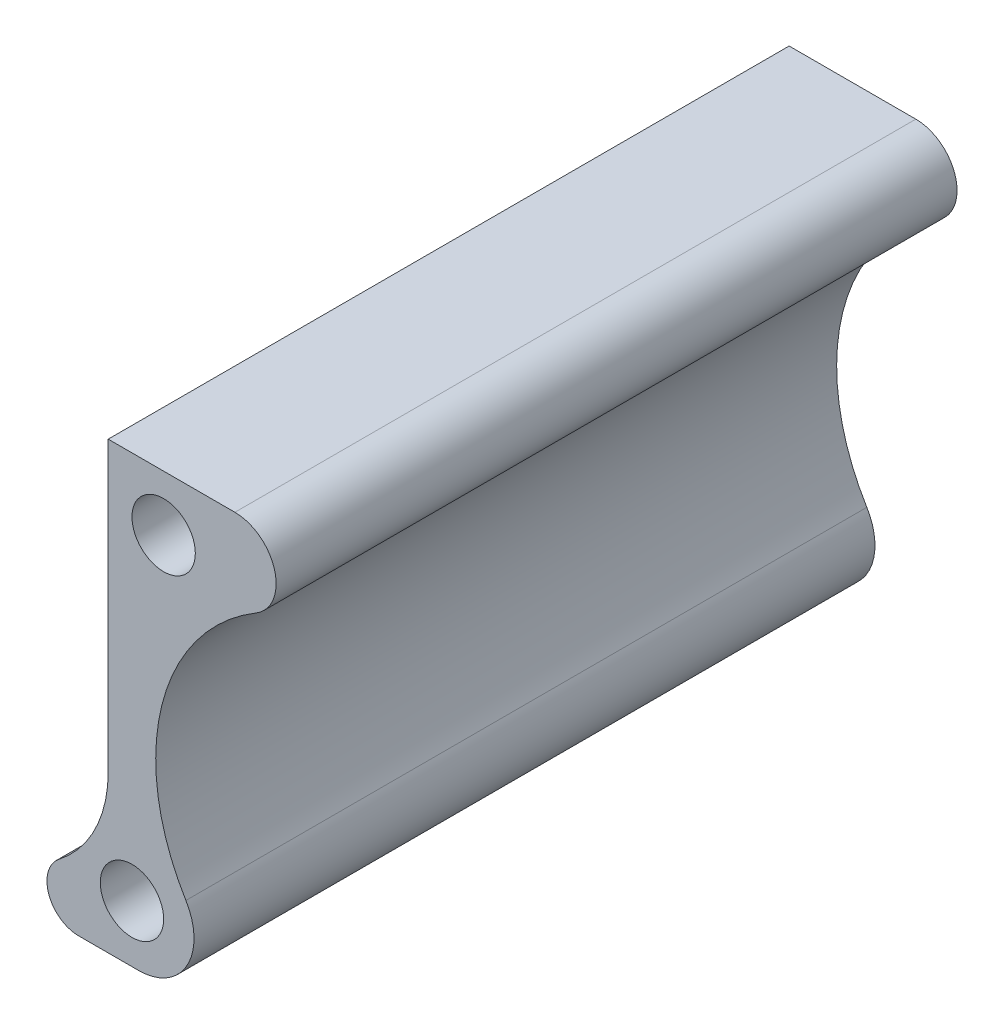
SolidWorks part; units mm, degrees
ref_plane "Front Plane" through (0, 0, 0) normal (0, 0, 1) x (1, 0, 0)
ref_plane "Top Plane" through (0, 0, 0) normal (0, 1, 0) x (1, 0, 0)
ref_plane "Right Plane" through (0, 0, 0) normal (1, 0, 0) x (0, 0, -1)
sketch "Sketch1" plane through (0, 0, 0) normal (0, 0, 1) x (1, 0, 0)
  line L0 (-16, 38) -> (16, 38)
  line L1 (-20.1, 6.5) -> (20.1, 6.5) construction
  line L2 (-20.1, 6.5) -> (-20.1, 2.3) construction
  line L3 (-20.1, 2.3) -> (20.1, 2.3) construction
  line L4 (20.1, 6.5) -> (20.1, 2.3) construction
  line L5 (-20.1, 6.5) -> (20.1, 2.3) construction
  line L6 (-20.1, 2.3) -> (20.1, 6.5) construction
  line L7 (-26.1, 7) -> (26.1, 7) construction
  line L8 (-26.1, 7) -> (-26.1, 1.8) construction
  line L9 (-26.1, 1.8) -> (26.1, 1.8) construction
  line L10 (26.1, 7) -> (26.1, 1.8) construction
  line L11 (-26.1, 7) -> (26.1, 1.8) construction
  line L12 (-26.1, 1.8) -> (26.1, 7) construction
  line L13 (29.1, 9.9) -> (-29.1, 9.9) construction
  line L14 (29.1, 9.9) -> (29.1, -1.1) construction
  line L15 (29.1, -1.1) -> (-29.1, -1.1) construction
  line L16 (-29.1, 9.9) -> (-29.1, -1.1) construction
  line L17 (29.1, 9.9) -> (-29.1, -1.1) construction
  line L18 (29.1, -1.1) -> (-29.1, 9.9) construction
  line L19 (32.1, 11.8) -> (-32.1, 11.8) construction
  line L20 (32.1, 11.8) -> (32.1, -3) construction
  line L21 (32.1, -3) -> (-32.1, -3) construction
  line L22 (-32.1, 11.8) -> (-32.1, -3) construction
  line L23 (32.1, 11.8) -> (-32.1, -3) construction
  line L24 (32.1, -3) -> (-32.1, 11.8) construction
  line L25 (16, 38) -> (16, 11.8)
  line L26 (-16, 38) -> (-16, 11.8)
  line L27 (-16, 11.8) -> (-32.1, 11.8)
  line L28 (-32.1, 11.8) -> (-32.1, 3)
  line L29 (-32.1, 3) -> (-29.1, 3)
  line L30 (-29.1, 3) -> (-29.1, 9.9)
  line L31 (-29.1, 9.9) -> (29.1, 9.9)
  line L32 (29.1, 9.9) -> (29.1, 3)
  line L33 (29.1, 3) -> (32.1, 3)
  line L34 (32.1, 3) -> (32.1, 11.8)
  line L35 (32.1, 11.8) -> (16, 11.8)
  line L37 (-21, 6.9) -> (21, 6.9) construction
  line L38 (-21, 6.9) -> (-21, 1.9) construction
  line L39 (-21, 1.9) -> (21, 1.9) construction
  line L40 (21, 6.9) -> (21, 1.9) construction
  line L41 (-21, 6.9) -> (21, 1.9) construction
  line L42 (-21, 1.9) -> (21, 6.9) construction
  circle A0 centre (0, 22) radius 8 construction
  circle A1 centre (0, 22) radius 13
  point P2 (0, 4.4)
  point P5 (0, 4.4)
  point P13 (0, 4.4)
  point P18 (0, 4.4)
  point P34 (0, 4.4)
  dimension "D1" = 16
  dimension "D11" = 26
  dimension "D2" = 40.2
  dimension "D3" = 4.2
  dimension "D4" = 6
  dimension "D5" = 0.5
  dimension "D6" = 3
  dimension "D7" = 1.9
  dimension "D8" = 3
  dimension "D9" = 8.8
  dimension "D10" = 3
  dimension "D12" = 22
  dimension "D13" = 16
  dimension "D14" = 32
  dimension "D15" = 16
  dimension "D17" = 42
  dimension "D18" = 5
  dimension "D19" = 6
extrude "Boss-Extrude1" add sketch "Sketch1" along normal blind 43 contours A1 L31 L32 L33 L34 L35 L25 L0 L26 L27 L28 L29 L30 region at (0, 37.2688, 0)
fillet "Fillet3" radius 8 2 edges at (16, 11.8, 21.5) (-16, 11.8, 21.5)
sketch "Sketch5" plane through (0, 0, 0) normal (0, 0, -1) x (-1, 0, 0)
  line L3 (16, 38) -> (-16, 38) construction
  line L4 (-16, 38) -> (-16, 19.8) construction
  line L5 (16, 38) -> (16, 19.8) construction
  circle A0 centre (-12.5, 34.5) radius 2
  circle A1 centre (12.5, 34.5) radius 2
  circle A2 centre (-14.5, 13.5) radius 2
  circle A3 centre (14.5, 13.5) radius 2
  dimension "D1" = 4
  dimension "D5" = 24.5
  dimension "D2" = 3.5
  dimension "D3" = 3.5
  dimension "D4" = 3.5
  dimension "D6" = 1.5
  dimension "D7" = 1.5
extrude "Cut-Extrude5" cut sketch "Sketch5" against normal up to next
fillet "Fillet1" radius 1.5 2 edges at (29.1, 9.9, 21.5) (-29.1, 9.9, 21.5)
fillet "Fillet2" radius 3 2 edges at (32.1, 11.8, 21.5) (-32.1, 11.8, 21.5)
fillet "Fillet4" radius 3.5 2 edges at (-4.7529, 9.9, 21.5) (4.7529, 9.9, 21.5)
sketch "Sketch6" plane through (0, 0, 43) normal (0, 0, 1) x (1, 0, 0)
  line L0 (-16, 38) -> (-16, 19.8) construction
  line L1 (-16, 19.8) -> (-16, 38)
  line L2 (-16, 38) -> (-8, 38)
  line L3 (-16, 38) -> (16, 38) construction
  line L4 (-14.0815, 9.9) -> (-17.8689, 9.9)
  line L5 (-27.6, 9.9) -> (-14.0815, 9.9) construction
  arc A0 (-11.0946, 15.2242) -> (-14.0815, 9.9) centre (-14.0815, 13.4) cw
  arc A1 (-19.0951, 13.48) -> (-16, 19.8) centre (-24, 19.8) ccw
  arc A2 (-8, 38) -> (-6.6652, 33.1613) centre (-8, 35.3966) cw
  arc A3 (-11.0946, 15.2242) -> (-6.6652, 33.1613) centre (0, 22) cw
  arc A4 (11.0946, 15.2242) -> (-11.0946, 15.2242) centre (0, 22) ccw construction
  arc A5 (-19.0951, 13.48) -> (-17.8689, 9.9) centre (-17.8689, 11.9) ccw
  arc A7 (-24, 11.8) -> (-16, 19.8) centre (-24, 19.8) ccw construction
  dimension "D2" = 2
  dimension "D1" = 8
extrude "Cut-Extrude6" cut sketch "Sketch6" against normal up to next (43 mm away) flip side to cut
